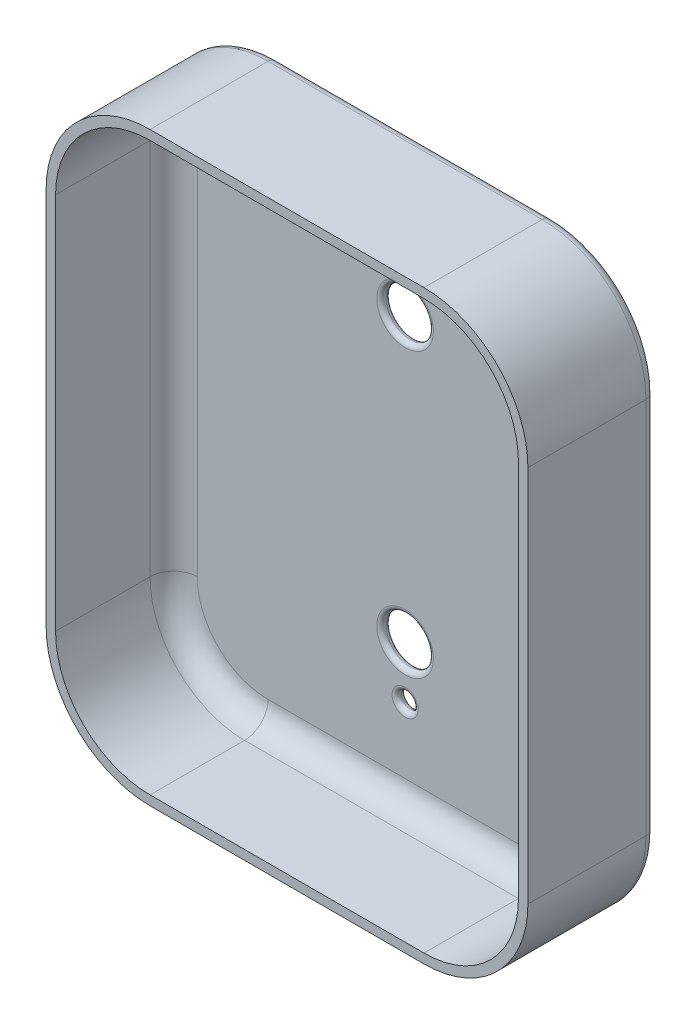
SolidWorks part; units mm, degrees
ref_plane "Front Plane" through (0, 0, 0) normal (0, 0, 1) x (1, 0, 0)
ref_plane "Top Plane" through (0, 0, 0) normal (0, 1, 0) x (1, 0, 0)
ref_plane "Right Plane" through (0, 0, 0) normal (1, 0, 0) x (0, 0, -1)
sketch "Sketch4" plane through (0, 0, 0) normal (0, 0, 1) x (1, 0, 0)
  line L1 (-37.5, 55) -> (37.5, 55)
  line L2 (-37.5, 55) -> (-37.5, -55)
  line L3 (-37.5, -55) -> (37.5, -55)
  line L4 (37.5, 55) -> (37.5, -55)
  line L5 (-28.5, 50) -> (28.5, 50)
  line L6 (-28.5, 50) -> (-28.5, -50)
  line L7 (-28.5, -50) -> (28.5, -50)
  line L8 (28.5, 50) -> (28.5, -50)
  point P4 (-37.5, 0)
  point P6 (0, 55)
  point P11 (0, 50)
  point P12 (-28.5, 0)
  dimension "D1" = 75
  dimension "D2" = 110
  dimension "D3" = 57
  dimension "D4" = 100
sketch "Sketch1" plane through (0, 0, 0) normal (0, 0, 1) x (1, 0, 0)
  line L0 (0, 60) -> (0, -60) construction
  line L5 (-29, 60) -> (29, 60)
  line L6 (-49, 40) -> (-49, -40)
  line L7 (-29, -60) -> (29, -60)
  line L8 (49, 40) -> (49, -40)
  line L9 (-49, 0) -> (49, 0) construction
  line L10 (-29, 62) -> (29, 62)
  line L11 (51, 40) -> (51, -40)
  line L12 (-29, -62) -> (29, -62)
  line L13 (-51, 40) -> (-51, -40)
  arc A2 (49, 40) -> (29, 60) centre (29, 40) ccw
  arc A3 (49, -40) -> (29, -60) centre (29, -40) cw
  arc A4 (-29, -60) -> (-49, -40) centre (-29, -40) cw
  arc A5 (-49, 40) -> (-29, 60) centre (-29, 40) cw
  arc A6 (51, 40) -> (29, 62) centre (29, 40) ccw
  arc A7 (51, -40) -> (29, -62) centre (29, -40) cw
  arc A8 (-29, -62) -> (-51, -40) centre (-29, -40) cw
  arc A9 (-51, 40) -> (-29, 62) centre (-29, 40) cw
  point P17 (49, 60)
  point P23 (-49, -60)
  point P26 (-49, 60)
  dimension "D5" = 20
  dimension "D3" = 98
  dimension "D4" = 120
  dimension "D6" = 2
sketch "Sketch3" plane through (0, 0, 0) normal (0, 0, 1) x (1, 0, 0)
  line L0 (-44, -20) -> (-44, 20)
  line L1 (-44, -20) -> (44, -20)
  line L2 (44, -20) -> (44, 20)
  line L3 (-44, 20) -> (44, 20)
  line L4 (-44, 0) -> (44, 0) construction
  line L5 (0, 20) -> (0, -20) construction
  line L6 (-38, 16.75) -> (-38, 0) construction
  line L7 (38, -16.75) -> (38, 0) construction
  line L8 (-38, 16.75) -> (0, 16.75) construction
  line L9 (38, -16.75) -> (0, -16.75) construction
  circle A3 centre (-38, 16.75) radius 1
  circle A4 centre (38, -16.75) radius 1
  dimension "D5" = 2
  dimension "D1" = 88
  dimension "D2" = 40
  dimension "D3" = 76
  dimension "D4" = 33.5
sketch "Sketch6" plane through (0, 0, 0) normal (0, 0, 1) x (1, 0, 0)
  line L0 (-29, 62) -> (29, 62)
  line L1 (51, 40) -> (51, -40)
  line L2 (-29, -62) -> (29, -62)
  line L3 (-51, 40) -> (-51, -40)
  line L6 (0, 0) -> (7.7555, 0) construction
  arc A0 (51, 40) -> (29, 62) centre (29, 40) ccw
  arc A1 (51, -40) -> (29, -62) centre (29, -40) cw
  arc A2 (-29, -62) -> (-51, -40) centre (-29, -40) cw
  arc A3 (-51, 40) -> (-29, 62) centre (-29, 40) cw
  circle A4 centre (0, 41) radius 1.75
  circle A5 centre (0, -41) radius 1.75
  circle A6 centre (0, 30) radius 5
  circle A7 centre (0, -30) radius 5
  dimension "D2" = 3.5
  dimension "D3" = 10
  dimension "D1" = 82
  dimension "D4" = 30
extrude "Boss-Extrude7" add sketch "Sketch1" along normal blind 25
extrude "Boss-Extrude9" add sketch "Sketch6" against normal blind 2
fillet "Fillet1" radius 5 8 edges at (0, -60, 0) (-43.1421, -54.1421, 0) (-49, 0, 0) (-43.1421, 54.1421, 0) (0, 60, 0) (43.1421, 54.1421, 0) (49, 0, 0) (43.1421, -54.1421, 0)
fillet "Fillet2" radius 2 8 edges at (51, 0, -2) (44.5563, 55.5563, -2) (0, 62, -2) (-44.5563, 55.5563, -2) (44.5563, -55.5563, -2) (0, -62, -2) (-44.5563, -55.5563, -2) (-51, 0, -2)
fillet "Fillet3" radius 1 8 edges at (1.75, -41, -2) (1.75, -41, 0) (5, -30, -2) (5, -30, 0) (5, 30, 0) (5, 30, -2) (1.75, 41, 0) (1.75, 41, -2)
